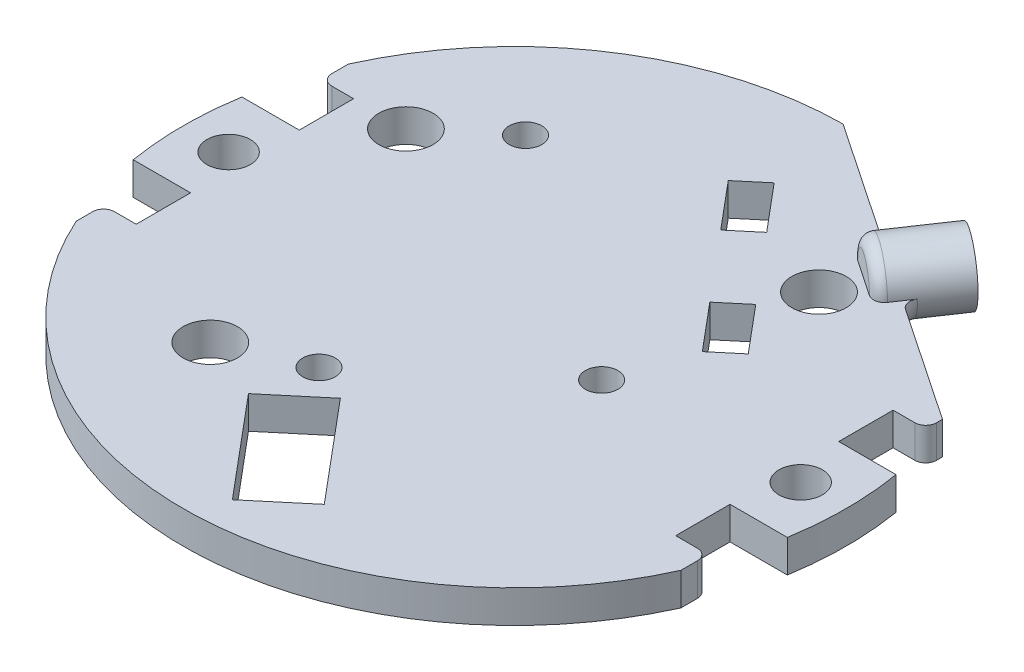
SolidWorks part; units mm, degrees
ref_plane "Alzado" through (0, 0, 0) normal (0, 0, 1) x (1, 0, 0)
ref_plane "Planta" through (0, 0, 0) normal (0, 1, 0) x (1, 0, 0)
ref_plane "Vista lateral" through (0, 0, 0) normal (1, 0, 0) x (0, 0, -1)
sketch "Croquis1" plane through (0, 0, 0) normal (0, 1, 0) x (1, 0, 0)
  circle A0 centre (0, 0) radius 30.5
extrude "Saliente-Extruir1" add sketch "Croquis1" along normal blind 3
sketch "Croquis5" plane through (0, 3, 0) normal (0, 1, 0) x (1, 0, 0)
  line L0 (0, 0) -> (0, 10)
  line L1 (28.8141, -5) -> (30.0874, -5)
  line L2 (28.8141, 5) -> (30.0874, 5)
  line L3 (-24.8141, 10) -> (-28.8141, 10)
  line L4 (24.8141, -5) -> (24.8141, -10)
  line L5 (-24.8141, -10) -> (-28.8141, -10)
  line L6 (24.8141, -5) -> (28.8141, -5)
  line L7 (24.8141, 5) -> (24.8141, 10)
  line L8 (-24.8141, 5) -> (-28.8141, 5)
  line L9 (-24.8141, 5) -> (-24.8141, 10)
  line L10 (-24.8141, -5) -> (-28.8141, -5)
  line L11 (-24.8141, -5) -> (-24.8141, -10)
  line L12 (24.8141, 5) -> (28.8141, 5)
  line L13 (24.8141, -10) -> (28.8141, -10)
  line L14 (24.8141, 10) -> (28.8141, 10)
  line L15 (-28.8141, 5) -> (-30.0874, 5)
  line L16 (-28.8141, -5) -> (-30.0874, -5)
  circle A1 centre (0, 0) radius 30.5 construction
  arc A2 (-28.8141, 10) -> (-30.0874, 5) centre (0, 0) ccw
  arc A3 (28.8141, 10) -> (28.8141, -10) centre (0, 0) cw
  arc A4 (-30.0874, -5) -> (-28.8141, -10) centre (0, 0) ccw
  arc A5 (30.0874, -5) -> (28.8141, -10) centre (0, 0) cw
  arc A6 (28.8141, 10) -> (30.0874, 5) centre (0, 0) cw
  circle M2 centre (0, 0) radius 30.5
extrude "Cortar-Extruir3" cut sketch "Croquis5" against normal blind 4 contours L11 L10 L8 L9 L3 L5 M2 | L15 L8 L9 L3 M2 | L14 L7 L12 L2 M2 | L4 L13 L1 L6 M2 region at (27.1844, 3, 7.3876) region at (27.1844, 3, -7.3876) region at (-27.1844, 3, 7.3876) region at (-27.1844, 3, -7.3876)
sketch "Croquis7" plane through (0, 3, 0) normal (0, 1, 0) x (1, 0, 0)
  line L0 (-8.1011, 29.1011) -> (9.5756, 8.0348)
  line L1 (9.5756, 8.0348) -> (27.2522, -13.0314)
  line L2 (-8.1011, 29.1011) -> (-27.2522, 13.0314)
  line L3 (27.2522, -13.0314) -> (8.1011, -29.1011)
  line L4 (8.1011, -29.1011) -> (-27.2522, 13.0314)
  line L5 (1.4284, 22.4114) -> (-0.8697, 20.4831)
  line L6 (1.4284, 22.4114) -> (4.6423, 18.5812)
  line L7 (4.6423, 18.5812) -> (2.3442, 16.6528)
  line L8 (2.3442, 16.6528) -> (-0.8697, 20.4831)
  line L9 (7.9686, 9.95) -> (11.1825, 6.1197)
  line L10 (8.1011, -29.1011) -> (5.53, -26.0369)
  line L11 (10.2667, 11.8783) -> (13.4807, 8.0481)
  line L12 (13.4807, 8.0481) -> (11.1825, 6.1197)
  line L13 (10.2667, 11.8783) -> (7.9686, 9.95)
  line L14 (5.53, -26.0369) -> (10.8923, -21.5374)
  line L15 (10.8923, -21.5374) -> (-19.3188, 14.4667)
  line L17 (-24.6811, 9.9672) -> (-19.3188, 14.4667)
  point P7 (-9.5756, -8.0348)
extrude "Cortar-Extruir5" cut sketch "Croquis7" against normal blind 4 contours L7 L6 L5 L0 | L11 L13 L0 L1 L12 region at (1.8863, 3, -19.5321) region at (10.7246, 3, -8.999)
sketch "Croquis8" plane through (0, 3, 0) normal (0, 1, 0) x (1, 0, 0)
  line L0 (-11.3137, 11.3137) -> (0, 0)
  line L2 (0, 0) -> (12, 0)
  line L3 (0, 0) -> (-11.3137, 11.3137)
  line L4 (12, 0) -> (12, 16)
  line L5 (0, 0) -> (-12, 0)
  line L6 (-12, 0) -> (-12, -16)
  line L10 (1.5586, -27.5246) -> (6.1549, -23.6679)
  line L11 (6.1549, -23.6679) -> (-1.5586, -14.4754)
  line L13 (-6.1549, -18.3321) -> (-1.5586, -14.4754)
  line L14 (1.5586, -27.5246) -> (-6.1549, -18.3321)
  circle A0 centre (0, 0) radius 30
  circle A1 centre (9, -1) radius 1.5
  circle A2 centre (-5, -13) radius 1.5
  circle A3 centre (-12, -16) radius 2.5
  circle A4 centre (-14, 15) radius 1.5
  circle A5 centre (12, 16) radius 2.5
  point P20 (-3.8567, -16.4037)
extrude "Cortar-Extruir6" cut sketch "Croquis8" against normal blind 10 contours L13 L10 L11 | A3 | L6 A3 | A3 L6 | A5 | L4 A5 | A5 L4 | L14 L10 L11 | L14 L11 | L13 L11 | A4 | L2 A1 | L2 A1 | A2 region at (10.2822, 3, -17.7178) region at (9, 3, -0.2032) region at (9, 3, 1.148) region at (-10.2822, 3, 14.2822) region at (0, 3, 21) region at (-5, 3, 13) region at (-14, 3, -15)
sketch "Croquis10" plane through (0, 3, 0) normal (0, 1, 0) x (1, 0, 0)
  line L0 (-24.8141, 10) -> (-27.8141, 10)
  line L2 (-24.8141, 10) -> (-28.8141, 10) construction
  line L4 (-27.8141, 10) -> (-27.8141, 12.5151)
  line L6 (-27.8141, 10) -> (-28.8141, 10)
  line L14 (-27.8141, -10) -> (-28.8141, -10)
  line L15 (-27.8141, -10) -> (-27.8141, -12.5151)
  line L16 (27.8141, -10) -> (27.8141, -12.5151)
  line L17 (27.8141, -10) -> (28.8141, -10)
  line L21 (27.8141, 10) -> (28.8141, 10)
  line L22 (27.8141, 10) -> (27.8141, 12.5151)
  line L23 (24.8141, 10) -> (27.8141, 10)
  circle A0 centre (-26.3141, 0) radius 2
  circle A1 centre (26.3141, 0) radius 2
  arc A2 (28.8141, 10) -> (-28.8141, 10) centre (0, 0) ccw construction
  arc A5 (-27.8141, 12.5151) -> (-28.8141, 10) centre (0, 0) ccw
  arc A7 (-27.8141, -12.5151) -> (-28.8141, -10) centre (0, 0) cw
  arc A8 (27.8141, -12.5151) -> (28.8141, -10) centre (0, 0) ccw
  arc A10 (27.8141, 12.5151) -> (28.8141, 10) centre (0, 0) cw
  line M13 (24.8141, 10) -> (28.8141, 10)
  arc M14 (28.8141, 10) -> (-28.8141, 10) centre (0, 0) ccw
  line M15 (-28.8141, 10) -> (-24.8141, 10)
  line M21 (-24.8141, -10) -> (-28.8141, -10)
  arc M22 (-28.8141, -10) -> (28.8141, -10) centre (0, 0) ccw
  line M23 (28.8141, -10) -> (24.8141, -10)
extrude "Cortar-Extruir8" cut sketch "Croquis10" against normal blind 3 contours L15 M21 M22 | L4 M15 M14 | L16 M23 M22 | L22 M13 M14 | A0 | A1 | L22 A10 L21 region at (-28.1547, 3, -10.8559) region at (28.1547, 3, -10.8559) region at (-28.1547, 3, 10.8559) region at (28.1547, 3, 10.8559) region at (-26.3141, 3, 0) region at (26.3141, 3, 0)
sketch "Croquis11" plane through (0, 3, 0) normal (0, 1, 0) x (1, 0, 0)
  line L0 (0, 0) -> (-20, 0)
  line L1 (-20, 0) -> (-20, 10)
  line L2 (0, 0) -> (0, 4.5949)
  line L3 (29.8013, 10.2046) -> (-1.7022, 31.454)
  circle A0 centre (-20, 10) radius 2.5
  circle A5 centre (0, 0) radius 31.5
  line M20 (27.8141, 10) -> (27.8141, 12.5151)
  arc M21 (27.8141, 12.5151) -> (-27.8141, 12.5151) centre (0, 0) ccw
extrude "Cortar-Extruir9" cut sketch "Croquis11" against normal blind 3 contours L3 M20 M21 | A0 region at (15.2326, 3, -22.6507) region at (-18.2822, 3, -8.2822)
sketch "Croquis13" plane through (14.0495, 0, -20.8293) normal (0.5592, 0, -0.829) x (-0.829, 0, -0.5592)
  line L1 (-16.603, 0) -> (17.2916, 0)
  line L2 (-16.603, 0) -> (-16.603, 3)
  line L3 (-16.603, 3) -> (17.2916, 3)
  line L4 (17.2916, 0) -> (17.2916, 3)
extrude "Saliente-Extruir2" add sketch "Croquis13" along normal blind 6
sketch "Croquis14" plane through (17.4047, 0, -25.8035) normal (0.5592, 0, -0.829) x (-0.829, 0, -0.5592)
  circle A0 centre (0.0043, 3) radius 3
extrude "Saliente-Extruir3" add sketch "Croquis14" against normal blind 8
sketch "Croquis17" plane through (17.4047, 0, -25.8035) normal (0.5592, 0, -0.829) x (-0.829, 0, -0.5592)
  circle A0 centre (0.0043, 3) radius 1.5
extrude "Cortar-Extruir10" cut sketch "Croquis17" against normal blind 7
sketch "Croquis19" plane through (17.4047, 0, -25.8035) normal (0.5592, 0, -0.829) x (-0.829, 0, -0.5592)
  line L0 (3.0043, 3) -> (17.2916, 3)
  line L1 (17.2916, 3) -> (17.2916, 0)
  line L2 (17.2916, 0) -> (-16.603, 0)
  line L3 (-16.603, 0) -> (-16.603, 3)
  line L4 (-16.603, 3) -> (-2.9957, 3)
  arc A0 (3.0043, 3) -> (-2.9957, 3) centre (0.0043, 3) ccw
extrude "Cortar-Extruir11" cut sketch "Croquis19" against normal blind 6
sketch "Croquis20" plane through (14.0495, 0, -20.8293) normal (0.5592, 0, -0.829) x (-0.829, 0, -0.5592)
  circle A0 centre (0.0043, 3) radius 1.5
  circle A1 centre (0.0043, 3) radius 3
extrude "Saliente-Extruir4" add sketch "Croquis20" along normal blind 5
fillet "Redondeo1" radius 1 1 edges at (12.9276, 6, -19.1736)
fillet "Redondeo2" radius 1 2 edges at (15.8046, 0.8787, -19.6455) (12.2873, 0.8787, -22.0179)
sketch "Croquis21" plane through (0, 3, 0) normal (0, 1, 0) x (1, 0, 0)
  line L0 (7.9686, 9.95) -> (10.2667, 11.8783)
  line L1 (7.9686, 9.95) -> (7.7758, 10.1798)
  line L2 (10.2667, 11.8783) -> (10.0739, 12.1081)
  line L3 (7.7758, 10.1798) -> (10.0739, 12.1081)
  line L4 (11.1825, 6.1197) -> (13.4807, 8.0481)
  line L5 (11.1825, 6.1197) -> (11.3754, 5.8899)
  line L6 (13.4807, 8.0481) -> (13.6735, 7.8183)
  line L7 (11.3754, 5.8899) -> (13.6735, 7.8183)
  line L8 (2.3442, 16.6528) -> (4.6423, 18.5812)
  line L9 (2.3442, 16.6528) -> (2.537, 16.423)
  line L10 (4.6423, 18.5812) -> (4.8352, 18.3514)
  line L11 (2.537, 16.423) -> (4.8352, 18.3514)
  line L12 (-0.8697, 20.4831) -> (1.4284, 22.4114)
  line L13 (-0.8697, 20.4831) -> (-1.0626, 20.7129)
  line L14 (1.4284, 22.4114) -> (1.2356, 22.6412)
  line L15 (-1.0626, 20.7129) -> (1.2356, 22.6412)
extrude "Cortar-Extruir12" cut sketch "Croquis21" against normal blind 3
fillet "Redondeo3" radius 1 4 edges at (-27.8141, 1.5, 10) (-27.8141, 1.5, -10) (27.8141, 1.5, 10) (27.8141, 1.5, -10)
